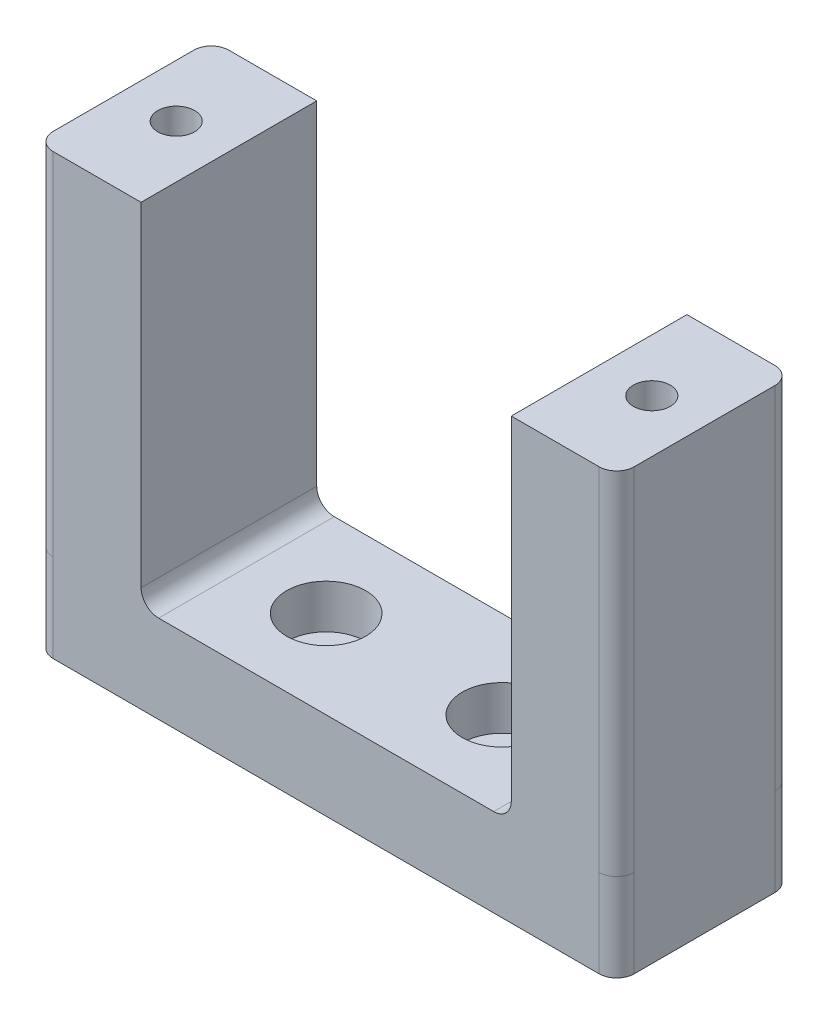
SolidWorks part; units mm, degrees
ref_plane "Front Plane" through (0, 0, 0) normal (0, 0, 1) x (1, 0, 0)
ref_plane "Top Plane" through (0, 0, 0) normal (0, 1, 0) x (1, 0, 0)
ref_plane "Right Plane" through (0, 0, 0) normal (1, 0, 0) x (0, 0, -1)
sketch "Sketch1" plane through (0, 0, 0) normal (0, 1, 0) x (1, 0, 0)
  line L1 (2, 0) -> (64.15, 0)
  line L2 (0, 2) -> (0, 18)
  line L3 (2, 20) -> (64.15, 20)
  line L4 (66.15, 2) -> (66.15, 18)
  arc A0 (0, 2) -> (2, 0) centre (2, 2) ccw
  arc A1 (64.15, 0) -> (66.15, 2) centre (64.15, 2) ccw
  arc A2 (66.15, 18) -> (64.15, 20) centre (64.15, 18) ccw
  arc A3 (2, 20) -> (0, 18) centre (2, 18) ccw
  point P7 (0, 0)
  point P12 (66.15, 20)
  point P15 (0, 20)
  dimension "D3" = 2
  dimension "D1" = 20
  dimension "D2" = 66.15
extrude "Boss-Extrude1" add sketch "Sketch1" along normal blind 10
sketch "Sketch2" plane through (0, 10, 0) normal (0, 1, 0) x (1, 0, 0)
  line L0 (64.15, 20) -> (2, 20) construction
  line L1 (0, 20) -> (12, 20)
  line L2 (0, 20) -> (0, 0)
  line L3 (0, 0) -> (12, 0)
  line L4 (12, 20) -> (12, 0)
  line L5 (2, 0) -> (64.15, 0) construction
  line L6 (12, 10) -> (54.15, 10) construction
  line L7 (54.15, 20) -> (66.15, 20)
  line L8 (54.15, 20) -> (54.15, 0)
  line L9 (54.15, 0) -> (66.15, 0)
  line L10 (66.15, 20) -> (66.15, 0)
  point P14 (33.075, 10)
  point P15 (33.075, 0)
  dimension "D1" = 12
  dimension "D2" = 42.15
extrude "Boss-Extrude2" add sketch "Sketch2" along normal blind 40
sketch "Sketch3" plane through (0, 50, 0) normal (0, 1, 0) x (1, 0, 0)
  line L0 (6, 20) -> (6, 0) construction
  line L1 (12, 20) -> (0, 20) construction
  line L2 (0, 0) -> (12, 0) construction
  line L3 (60.15, 20) -> (60.15, 0) construction
  line L4 (66.15, 20) -> (54.15, 20) construction
  line L5 (54.15, 0) -> (66.15, 0) construction
  circle A0 centre (6, 10) radius 2.1
  circle A1 centre (60.15, 10) radius 2.1
  dimension "D1" = 4.2
extrude "Cut-Extrude1" cut sketch "Sketch3" against normal through all
sketch "Sketch4" plane through (0, 0, 0) normal (0, -1, 0) x (-1, 0, 0)
  line L1 (-8.1218, 13.675) -> (-10.2435, 10)
  line L2 (-10.2435, 10) -> (-8.1218, 6.325)
  line L3 (-8.1218, 6.325) -> (-3.8782, 6.325)
  line L4 (-3.8782, 6.325) -> (-1.7565, 10)
  line L5 (-1.7565, 10) -> (-3.8782, 13.675)
  line L6 (-3.8782, 13.675) -> (-8.1218, 13.675)
  line L7 (-62.2718, 13.675) -> (-64.3935, 10)
  line L8 (-64.3935, 10) -> (-62.2718, 6.325)
  line L9 (-62.2718, 6.325) -> (-58.0282, 6.325)
  line L10 (-58.0282, 6.325) -> (-55.9065, 10)
  line L11 (-55.9065, 10) -> (-58.0282, 13.675)
  line L12 (-58.0282, 13.675) -> (-62.2718, 13.675)
  circle A0 centre (-6, 10) radius 3.675 construction
  circle A1 centre (-60.15, 10) radius 3.675 construction
  circle A2 centre (-6, 10) radius 2.1 construction
  dimension "D1" = 7.35
extrude "Cut-Extrude2" cut sketch "Sketch4" against normal offset from surface (44 mm away) 6 up to face at (6, 50, -7.9)
fillet "Fillet3" radius 2 4 edges at (0, 30, -20) (0, 30, 0) (66.15, 30, 0) (66.15, 30, -20)
fillet "Fillet4" radius 2 2 edges at (54.15, 10, -10) (12, 10, -10)
sketch "Sketch6" plane through (0, 10, 0) normal (0, 1, 0) x (1, 0, 0)
  line L0 (23.075, 10) -> (43.075, 10) construction
  line L1 (66.15, 2) -> (66.15, 18) construction
  line L2 (52.15, 20) -> (14, 20) construction
  circle A0 centre (23.075, 10) radius 2.6
  circle A1 centre (43.075, 10) radius 2.6
  circle A2 centre (43.075, 10) radius 4.5
  circle A3 centre (23.075, 10) radius 4.5
  point P4 (66.15, 10)
  point P5 (33.075, 10)
  point P8 (33.075, 20)
  dimension "D2" = 5.2
  dimension "D3" = 9
  dimension "D1" = 20
extrude "Cut-Extrude4" cut sketch "Sketch6" against normal blind 10 contours A0 | A1 region at (23.075, 10, -10) region at (43.075, 10, -10)
extrude "Cut-Extrude5" cut sketch "Sketch6<3>" against normal blind 5 and the other way blind 5
sketch "Sketch6<3>" plane through (0, 10, 0) normal (0, 1, 0) x (1, 0, 0) same geometry as "Sketch6"
